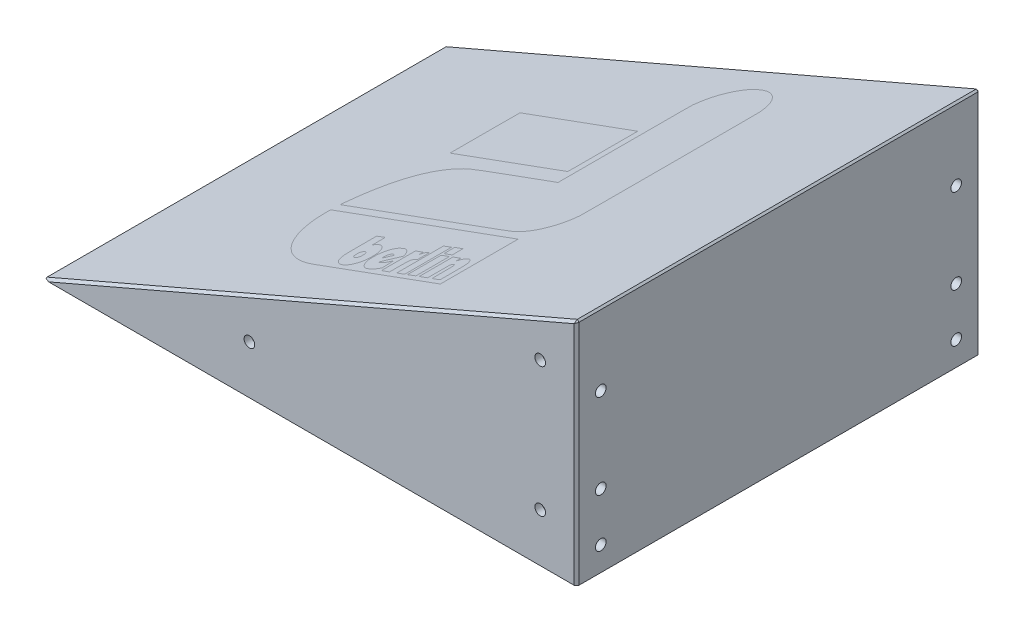
SolidWorks part; units mm, degrees
note: The reader was unsure of these and kept them because the rebuilt part matched: shared geometry of "Sketch16<3>".
ref_plane "Front Plane" through (0, 0, 0) normal (0, 0, 1) x (1, 0, 0)
ref_plane "Top Plane" through (0, 0, 0) normal (0, 1, 0) x (1, 0, 0)
ref_plane "Right Plane" through (0, 0, 0) normal (1, 0, 0) x (0, 0, -1)
sketch "Sketch1" plane through (0, 0, 0) normal (0, 0, 1) x (1, 0, 0)
  line L0 (0, 0) -> (-220.3974, 0)
  line L1 (-220.3974, 0) -> (0, 95)
  line L2 (0, 95) -> (0, 0)
  dimension "D1" = 240
extrude "Boss-Extrude1" add sketch "Sketch1" along normal blind 166.6667
ref_plane "Plane1" through (0, 0, 163.6667) normal (0, 0, 1) x (1, 0, 0)
sketch "Sketch2" plane through (0, 0, 163.6667) normal (0, 0, 1) x (1, 0, 0)
  line L0 (-5, 0) -> (-5, 87.4001)
  line L1 (-220.3974, 0) -> (0, 0) construction
  line L2 (-5, 87.4001) -> (-178.2213, 12.7348)
  line L3 (-178.2213, 12.7348) -> (-178.2213, 0)
  line L4 (-178.2213, 0) -> (-5, 0)
  line L5 (0, 95) -> (-220.3974, 0) construction
  line L6 (0, 0) -> (0, 95) construction
  dimension "D1" = 188.628
  dimension "D2" = 5
  dimension "D3" = 5
extrude "Cut-Extrude1" cut sketch "Sketch2" against normal offset from surface (160.6667 mm away) 3 up to face at (-73.4658, 31.6667, 0)
sketch "Sketch3" plane through (0, 0, 0) normal (1, 0, 0) x (0, 0, -1)
  line L0 (-156.6667, 0) -> (-156.6667, 95) construction
  line L1 (-166.6667, 0) -> (0, 0) construction
  line L2 (-166.6667, 95) -> (0, 95) construction
  line L3 (-166.6667, 0) -> (-166.6667, 95) construction
  line L4 (-83.3333, 95) -> (-83.3333, 0) construction
  line L5 (-10, 0) -> (-10, 95) construction
  circle A0 centre (-156.6667, 10) radius 2.2
  circle A1 centre (-156.6667, 65) radius 2.2
  circle A2 centre (-156.6667, 30) radius 2.2
  circle A3 centre (-10, 30) radius 2.2
  circle A4 centre (-10, 65) radius 2.2
  circle A5 centre (-10, 10) radius 2.2
  dimension "D2" = 4.4
  dimension "D3" = 10
  dimension "D4" = 20
  dimension "D5" = 30
  dimension "D1" = 10
extrude "Cut-Extrude2" cut sketch "Sketch3" against normal up to surface (5 mm away) up to face at (-5, 43.7, 83.3333)
sketch "Sketch4" plane through (0, 0, 0) normal (0, 0, -1) x (-1, 0, 0)
  line L0 (15, 0) -> (15, 88.5344) construction
  line L1 (220.3974, 0) -> (0, 0) construction
  line L2 (0, 95) -> (220.3974, 0) construction
  line L3 (0, 0) -> (0, 95) construction
  line L4 (15, 20) -> (135, 20) construction
  circle A0 centre (15, 73.5344) radius 2.2
  circle A1 centre (15, 20) radius 2.2
  circle A2 centre (135, 20) radius 2.2
  dimension "D1" = 4.4
  dimension "D2" = 20
  dimension "D3" = 15
  dimension "D4" = 15
  dimension "D5" = 120
extrude "Cut-Extrude3" cut sketch "Sketch4" against normal up to surface (163.6667 mm away)
ref_plane "Plane2" through (0, 0, 83.3333) normal (0, 0, -1) x (-1, 0, 0)
mirror "Mirror1" about plane through (0, 0, 83.3333) normal (0, 0, -1) of "Cut-Extrude3"
chamfer "Chamfer1" distance 1 angle 45 6 edges at (-220.3974, 0, 83.3333) (0, 95, 83.3333) (0, 47.5, 166.6667) (-110.1987, 47.5, 166.6667) (0, 47.5, 0) (-110.1987, 47.5, 0)
sketch "Sketch13" plane through (-166.8801, 23.068, 13.9635) normal (-0.3958, 0.9183, 0) x (0, 0, 1)
  line L0 (55.9477, 28.1093) -> (55.9477, 56.0832)
  line L1 (55.9477, 56.0832) -> (27.9739, 56.0832)
  line L2 (27.9739, 56.0832) -> (0, 56.0832)
  line L3 (0, 56.0832) -> (0, 96.1136)
  line L4 (0, 96.1136) -> (0, 136.144)
  line L5 (0, 136.144) -> (40.0304, 136.144)
  line L6 (40.0304, 136.144) -> (80.0608, 136.144)
  line L7 (80.0608, 136.144) -> (80.0608, 108.1701)
  line L8 (80.0608, 108.1701) -> (80.0608, 80.1962)
  line L9 (80.0608, 80.1962) -> (108.0347, 80.1962)
  line L10 (108.0347, 80.1962) -> (136.0085, 80.1962)
  line L11 (136.0085, 80.1962) -> (136.0085, 40.1658)
  line L12 (136.0085, 40.1658) -> (136.0085, 0.1354)
  line L13 (136.0085, 0.1354) -> (95.9781, 0.1354)
  line L14 (95.9781, 0.1354) -> (55.9477, 0.1354)
  line L15 (55.9477, 0.1354) -> (55.9477, 28.1093)
  line L16 (119.38, 5.285) -> (120.0235, 5.4406)
  line L17 (120.0235, 5.4406) -> (120.0235, 6.5278)
  line L18 (116.4971, 12.8693) -> (120.4299, 12.8693)
  line L19 (120.4299, 12.8693) -> (120.4288, 13.445)
  line L20 (119.3798, 5.285) -> (119.38, 5.285)
  line L21 (117.4134, 15.1659) -> (117.4853, 14.6304)
  line L22 (117.4853, 14.6304) -> (115.029, 14.6304)
  line L23 (130.3189, 17.2595) -> (130.3189, 18.5339)
  line L24 (130.3189, 18.5339) -> (129.0181, 18.7681)
  line L25 (84.9376, 11.9888) -> (84.9376, 18.6944)
  line L26 (84.9376, 18.6944) -> (83.3797, 18.6944)
  line L27 (83.3797, 18.6944) -> (81.8219, 18.6944)
  line L28 (81.8219, 18.6944) -> (81.8219, 11.9888)
  line L29 (81.8219, 11.9888) -> (81.8219, 5.2832)
  line L30 (81.8219, 5.2832) -> (83.3797, 5.2832)
  line L31 (83.3797, 5.2832) -> (84.9376, 5.2832)
  line L32 (84.9376, 5.2832) -> (84.9376, 11.9888)
  line L33 (95.7918, 15.6286) -> (96.1136, 15.2862)
  line L34 (96.1136, 15.2862) -> (96.1522, 10.2847)
  line L35 (96.1522, 10.2847) -> (96.1909, 5.2832)
  line L36 (96.1909, 5.2832) -> (97.744, 5.2832)
  line L37 (97.744, 5.2832) -> (99.2971, 5.2832)
  line L38 (99.2971, 5.2832) -> (99.2996, 8.5682)
  line L39 (103.4721, 10.1261) -> (103.5151, 5.2832)
  line L40 (103.5151, 5.2832) -> (105.0018, 5.2832)
  line L41 (105.0018, 5.2832) -> (106.4885, 5.2832)
  line L42 (106.4885, 5.2832) -> (106.4489, 10.7357)
  line L43 (99.574, 17.0612) -> (99.077, 16.2924)
  line L44 (99.077, 16.2924) -> (98.8423, 16.9531)
  line L45 (92.5097, 17.2277) -> (92.1175, 16.6093)
  line L46 (92.1175, 16.6093) -> (92.1175, 17.6519)
  line L47 (92.1175, 17.6519) -> (92.1175, 18.6944)
  line L48 (92.1175, 18.6944) -> (90.5597, 18.6944)
  line L49 (90.5597, 18.6944) -> (89.0018, 18.6944)
  line L50 (89.0018, 18.6944) -> (89.0018, 11.9888)
  line L51 (89.0018, 11.9888) -> (89.0018, 5.2832)
  line L52 (89.0018, 5.2832) -> (90.5503, 5.2832)
  line L53 (90.5503, 5.2832) -> (92.0987, 5.2832)
  line L54 (92.0987, 5.2832) -> (92.1453, 9.1101)
  line L55 (84.9376, 23.1648) -> (84.9376, 24.6549)
  line L56 (84.9376, 24.6549) -> (83.3797, 24.6549)
  line L57 (83.3797, 24.6549) -> (81.8219, 24.6549)
  line L58 (81.8219, 24.6549) -> (81.8219, 23.1648)
  line L59 (81.8219, 23.1648) -> (81.8219, 21.6746)
  line L60 (81.8219, 21.6746) -> (83.3797, 21.6746)
  line L61 (83.3797, 21.6746) -> (84.9376, 21.6746)
  line L62 (84.9376, 21.6746) -> (84.9376, 23.1648)
  line L63 (80.0277, 68.1058) -> (80.0623, 80.0608)
  line L64 (80.0623, 80.0608) -> (68.0727, 80.0608)
  line L65 (68.0727, 80.0608) -> (56.0832, 80.0608)
  line L66 (56.0832, 80.0608) -> (56.0832, 68.0712)
  line L67 (56.0832, 68.0712) -> (56.0832, 56.0817)
  line L68 (56.0832, 56.0817) -> (68.0381, 56.1163)
  line L69 (68.0381, 56.1163) -> (79.9931, 56.1509)
  line L70 (79.9931, 56.1509) -> (80.0277, 68.1058)
  line L71 (56.0832, 56.0817) -> (55.9477, 56.0832)
  line L72 (80.0623, 80.0608) -> (80.0608, 80.2508)
  spline S0 degree 3 poles (120.0235, 6.5278) (120.0235, 7.4768) (119.9954, 7.6043) (119.8028, 7.5304) knots 0 0 0 0 1 1 1 1
  spline S1 degree 3 poles (119.8028, 7.5304) (119.096, 7.2592) (118.2565, 7.1534) (117.2109, 7.2036) knots 0 0 0 0 1 1 1 1
  spline S2 degree 3 poles (117.2109, 7.2036) (116.2244, 7.2511) (115.9063, 7.3264) (115.3017, 7.6558) knots 0 0 0 0 1 1 1 1
  spline S3 degree 3 poles (115.3017, 7.6558) (113.9807, 8.3756) (112.9036, 9.9548) (112.5572, 11.6798) knots 0 0 0 0 1 1 1 1
  spline S4 degree 3 poles (112.5572, 11.6798) (112.3015, 12.9531) (112.024, 12.8693) (116.4971, 12.8693) knots 0 0 0 0 1 1 1 1
  spline S5 degree 3 poles (120.4288, 13.445) (120.4268, 15.0769) (119.8192, 16.8204) (118.9624, 17.6545) knots 0 0 0 0 1 1 1 1
  spline S6 degree 3 poles (118.9624, 17.6545) (118.689, 17.9206) (118.0996, 18.3072) (117.6526, 18.5136) knots 0 0 0 0 1 1 1 1
  spline S7 degree 3 poles (117.6526, 18.5136) (116.9232, 18.8503) (116.6868, 18.8893) (115.3496, 18.8932) knots 0 0 0 0 1 1 1 1
  spline S8 degree 3 poles (115.3496, 18.8932) (113.601, 18.8983) (112.619, 18.6494) (111.7388, 17.9781) knots 0 0 0 0 1 1 1 1
  spline S9 degree 3 poles (111.7388, 17.9781) (110.8801, 17.3232) (110.3098, 16.4939) (109.966, 15.4003) knots 0 0 0 0 1 1 1 1
  spline S10 degree 3 poles (109.966, 15.4003) (109.5683, 14.1354) (109.537, 11.2699) (109.9059, 9.889) knots 0 0 0 0 1 1 1 1
  spline S11 degree 3 poles (109.9059, 9.889) (110.5643, 7.4241) (112.0357, 5.8283) (114.2123, 5.2184) knots 0 0 0 0 1 1 1 1
  spline S12 degree 3 poles (114.2123, 5.2184) (115.0598, 4.9809) (118.2945, 5.0226) (119.3798, 5.285) knots 0 0 0 0 1 1 1 1
  spline S13 degree 3 poles (112.5728, 14.8379) (112.5728, 15.2621) (112.9536, 15.9345) (113.4314, 16.354) knots 0 0 0 0 1 1 1 1
  spline S14 degree 3 poles (113.4314, 16.354) (114.8968, 17.6406) (117.1726, 16.9616) (117.4134, 15.1659) knots 0 0 0 0 1 1 1 1
  spline S15 degree 3 poles (115.029, 14.6304) (112.9131, 14.6304) (112.5728, 14.6591) (112.5728, 14.8379) knots 0 0 0 0 1 1 1 1
  spline S16 degree 3 poles (128.0837, 5.1959) (130.1184, 5.7381) (131.1308, 6.9611) (131.1274, 8.873) knots 0 0 0 0 1 1 1 1
  spline S17 degree 3 poles (131.1274, 8.873) (131.1244, 10.659) (130.5305, 11.4345) (127.802, 13.2159) knots 0 0 0 0 1 1 1 1
  spline S18 degree 3 poles (127.802, 13.2159) (125.8156, 14.5128) (125.3067, 14.9859) (125.3067, 15.5356) knots 0 0 0 0 1 1 1 1
  spline S19 degree 3 poles (125.3067, 15.5356) (125.3067, 16.2783) (126.7192, 16.9245) (127.9105, 16.7268) knots 0 0 0 0 1 1 1 1
  spline S20 degree 3 poles (127.9105, 16.7268) (128.2293, 16.6739) (128.8784, 16.4854) (129.3529, 16.3078) knots 0 0 0 0 1 1 1 1
  spline S21 degree 3 poles (129.3529, 16.3078) (129.8275, 16.1303) (130.2389, 15.985) (130.2673, 15.985) knots 0 0 0 0 1 1 1 1
  spline S22 degree 3 poles (130.2673, 15.985) (130.2957, 15.985) (130.3189, 16.5585) (130.3189, 17.2595) knots 0 0 0 0 1 1 1 1
  spline S23 degree 3 poles (129.0181, 18.7681) (125.2165, 19.4526) (122.5963, 17.9842) (122.6016, 15.1722) knots 0 0 0 0 1 1 1 1
  spline S24 degree 3 poles (122.6016, 15.1722) (122.6047, 13.5145) (123.3273, 12.5517) (125.8526, 10.8401) knots 0 0 0 0 1 1 1 1
  spline S25 degree 3 poles (125.8526, 10.8401) (127.7723, 9.539) (128.2869, 9.0543) (128.2869, 8.5476) knots 0 0 0 0 1 1 1 1
  spline S26 degree 3 poles (128.2869, 8.5476) (128.2869, 7.2086) (125.4698, 6.9556) (122.8344, 8.0578) knots 0 0 0 0 1 1 1 1
  spline S27 degree 3 poles (122.8344, 8.0578) (122.6177, 8.1484) (122.5973, 8.0392) (122.5973, 6.7878) knots 0 0 0 0 1 1 1 1
  spline S28 degree 3 poles (122.5973, 6.7878) (122.5973, 5.7874) (122.6429, 5.4163) (122.7667, 5.4099) knots 0 0 0 0 1 1 1 1
  spline S29 degree 3 poles (122.7667, 5.4099) (122.8598, 5.4053) (123.3017, 5.3188) (123.7488, 5.2181) knots 0 0 0 0 1 1 1 1
  spline S30 degree 3 poles (123.7488, 5.2181) (124.8105, 4.9789) (127.2228, 4.9665) (128.0837, 5.1959) knots 0 0 0 0 1 1 1 1
  spline S31 degree 3 poles (92.1453, 9.1101) (92.1899, 12.7599) (92.207, 12.9747) (92.5133, 13.7498) knots 0 0 0 0 1 1 1 1
  spline S32 degree 3 poles (92.5133, 13.7498) (92.999, 14.9787) (93.5089, 15.6452) (94.1635, 15.9072) knots 0 0 0 0 1 1 1 1
  spline S33 degree 3 poles (94.1635, 15.9072) (94.8473, 16.1808) (95.3543, 16.0941) (95.7918, 15.6286) knots 0 0 0 0 1 1 1 1
  spline S34 degree 3 poles (99.2996, 8.5682) (99.3022, 12.0563) (99.4174, 13.0342) (99.9806, 14.3433) knots 0 0 0 0 1 1 1 1
  spline S35 degree 3 poles (99.9806, 14.3433) (100.5254, 15.6097) (101.6839, 16.3432) (102.5638, 15.9787) knots 0 0 0 0 1 1 1 1
  spline S36 degree 3 poles (102.5638, 15.9787) (103.3998, 15.6324) (103.4245, 15.4734) (103.4721, 10.1261) knots 0 0 0 0 1 1 1 1
  spline S37 degree 3 poles (106.4489, 10.7357) (106.4099, 16.0999) (106.4042, 16.1992) (106.0972, 16.8656) knots 0 0 0 0 1 1 1 1
  spline S38 degree 3 poles (106.0972, 16.8656) (105.5361, 18.0835) (104.6197, 18.7738) (103.367, 18.9222) knots 0 0 0 0 1 1 1 1
  spline S39 degree 3 poles (103.367, 18.9222) (101.906, 19.0952) (100.4161, 18.3642) (99.574, 17.0612) knots 0 0 0 0 1 1 1 1
  spline S40 degree 3 poles (98.8423, 16.9531) (98.5273, 17.84) (97.8459, 18.4967) (96.9708, 18.7566) knots 0 0 0 0 1 1 1 1
  spline S41 degree 3 poles (96.9708, 18.7566) (95.1569, 19.2952) (93.4499, 18.7102) (92.5097, 17.2277) knots 0 0 0 0 1 1 1 1
sketch "Sketch14" plane through (0, 0, 166.6667) normal (0, 0, 1) x (1, 0, 0)
  circle A0 centre (-135, 20) radius 2.85
  circle A1 centre (-15, 20) radius 2.85
  circle A2 centre (-15, 73.5344) radius 2.85
  dimension "D1" = 5.7
extrude "Einschmelzgewinde" [suppressed] cut sketch "Sketch14" against normal through all
chamfer "Chamfer2" [suppressed] distance 0.6 angle 45
sketch "Sketch16" plane through (-159.9623, 26.0499, 9.8989) normal (-0.3958, 0.9183, 0) x (0, 0, 1)
  line L0 (108.335, 94.9617) -> (108.3883, 95.2128)
  line L1 (108.3883, 95.2128) -> (124.4039, 95.2128)
  line L2 (124.4039, 95.2128) -> (140.4193, 95.2128)
  line L3 (140.4193, 95.2128) -> (140.4193, 94.9494)
  line L4 (119.0172, 42.3273) -> (119.2954, 41.6386)
  line L5 (119.2954, 41.6386) -> (116.6024, 41.6087)
  line L6 (116.6024, 41.6087) -> (113.9093, 41.5788)
  line L7 (113.9093, 41.5788) -> (113.7809, 40.1278)
  line L8 (113.5898, 37.9791) -> (113.5271, 37.2814)
  line L9 (113.5271, 37.2814) -> (119.8706, 37.2814)
  line L10 (128.4948, 60.8777) -> (128.1231, 60.82)
  line L11 (128.1231, 60.82) -> (128.6416, 60.2657)
  line L12 (135.3473, 66.6099) -> (135.4007, 66.861)
  line L13 (135.4007, 66.861) -> (131.7353, 66.861)
  line L14 (126.2622, 68.6507) -> (126.2183, 69.4283)
  line L15 (126.2183, 69.4283) -> (123.6492, 69.4283)
  line L16 (123.6492, 69.4283) -> (121.0801, 69.4283)
  line L17 (121.0801, 69.4283) -> (121.1565, 68.8528)
  line L18 (122.6716, 66.8701) -> (123.1739, 66.6427)
  line L19 (123.1739, 66.6427) -> (122.2495, 66.6402)
  line L20 (121.0826, 64.5448) -> (120.9319, 62.731)
  line L21 (120.9319, 62.731) -> (127.9311, 62.731)
  line L22 (127.9311, 62.731) -> (134.9303, 62.731)
  line L23 (134.9303, 62.731) -> (134.9938, 63.1496)
  line L24 (136.0281, 73.7537) -> (136.097, 74.4513)
  line L25 (136.097, 74.4513) -> (126.4447, 74.4513)
  line L26 (126.4447, 74.4513) -> (116.7925, 74.4513)
  line L27 (116.7925, 74.4513) -> (116.6573, 73.0281)
  line L28 (116.4561, 71.0189) -> (116.3901, 70.4329)
  line L29 (116.3901, 70.4329) -> (126.0443, 70.4329)
  line L30 (126.0443, 70.4329) -> (135.6986, 70.4329)
  line L31 (135.6986, 70.4329) -> (135.8289, 71.7445)
  line L32 (121.5481, 79.7835) -> (121.5554, 80.0371)
  line L33 (121.5554, 80.0371) -> (119.3509, 80.0068)
  line L34 (119.3509, 80.0068) -> (117.1463, 79.9766)
  line L35 (117.1463, 79.9766) -> (116.9582, 78.2464)
  line L36 (116.7628, 76.1512) -> (116.7557, 75.7861)
  line L37 (116.7557, 75.7861) -> (118.9602, 75.8163)
  line L38 (118.9602, 75.8163) -> (121.1647, 75.8465)
  line L39 (121.1647, 75.8465) -> (121.3527, 77.6883)
  line L40 (129.5857, 80.0053) -> (122.7274, 79.9765)
  line L41 (122.7274, 79.9765) -> (122.5423, 78.2464)
  line L42 (122.347, 76.1535) -> (122.3367, 75.7907)
  line L43 (122.3367, 75.7907) -> (129.2522, 75.7907)
  line L44 (129.2522, 75.7907) -> (136.1676, 75.7907)
  line L45 (136.1676, 75.7907) -> (136.2258, 76.1535)
  line L46 (137.7371, 91.7805) -> (137.7405, 92.199)
  line L47 (137.7405, 92.199) -> (132.7274, 92.199)
  line L48 (124.5456, 86.2731) -> (125.1453, 85.725)
  line L49 (125.1453, 85.725) -> (124.1875, 85.725)
  line L50 (122.8971, 82.0136) -> (122.895, 81.7067)
  line L51 (122.895, 81.7067) -> (129.8134, 81.7067)
  line L52 (129.8134, 81.7067) -> (136.7318, 81.7067)
  line L53 (136.7318, 81.7067) -> (136.7861, 81.9578)
  line L54 (70.7202, 71.6869) -> (70.7883, 72.2154)
  line L55 (70.7883, 72.2154) -> (43.3471, 72.2485)
  line L56 (99.7225, 44.2299) -> (95.6092, 1.4511)
  line L57 (95.6092, 1.4511) -> (95.3273, 1.4581)
  line L58 (34.5525, 68.1726) -> (34.6162, 68.647)
  line L59 (34.6162, 68.647) -> (49.0085, 68.647)
  line L60 (57.7572, 9.739) -> (57.7039, 9.4878)
  line L61 (57.7039, 9.4878) -> (43.3069, 9.4878)
  spline S0 degree 3 poles (99.9288, 1.0941) (99.3751, 1.126) (99.3428, 1.1445) (99.3424, 1.429) knots 0 0 0 0 1 1 1 1
  spline S1 degree 3 poles (99.3424, 1.429) (99.342, 1.8216) (108.2652, 94.6324) (108.335, 94.9617) knots 0 0 0 0 1 1 1 1
  spline S2 degree 3 poles (140.4193, 94.9494) (140.4193, 94.8046) (139.093, 80.8784) (137.4719, 64.0025) knots 0 0 0 0 1 1 1 1
  spline S3 degree 3 poles (137.4719, 64.0025) (135.8509, 47.1265) (134.4666, 32.6408) (134.3957, 31.812) knots 0 0 0 0 1 1 1 1
  spline S4 degree 3 poles (134.3957, 31.812) (133.88, 25.7773) (131.6141, 19.7739) (127.9922, 14.8456) knots 0 0 0 0 1 1 1 1
  spline S5 degree 3 poles (127.9922, 14.8456) (122.843, 7.8393) (115.2416, 3.113) (106.654, 1.5783) knots 0 0 0 0 1 1 1 1
  spline S6 degree 3 poles (106.654, 1.5783) (104.6505, 1.2203) (101.5789, 0.9991) (99.9288, 1.0941) knots 0 0 0 0 1 1 1 1
  spline S7 degree 3 poles (127.1959, 37.4526) (129.6932, 37.8881) (131.5617, 39.1703) (132.5472, 41.1247) knots 0 0 0 0 1 1 1 1
  spline S8 degree 3 poles (132.5472, 41.1247) (133.7329, 43.4761) (133.4378, 45.9391) (131.7703, 47.6089) knots 0 0 0 0 1 1 1 1
  spline S9 degree 3 poles (131.7703, 47.6089) (130.9869, 48.3934) (130.1037, 48.8893) (128.8626, 49.2415) knots 0 0 0 0 1 1 1 1
  spline S10 degree 3 poles (128.8626, 49.2415) (127.6313, 49.5909) (125.3664, 49.593) (124.0921, 49.2458) knots 0 0 0 0 1 1 1 1
  spline S11 degree 3 poles (124.0921, 49.2458) (121.9286, 48.6564) (119.9287, 47.1652) (119.1929, 45.5927) knots 0 0 0 0 1 1 1 1
  spline S12 degree 3 poles (119.1929, 45.5927) (118.6846, 44.5065) (118.6202, 43.3102) (119.0172, 42.3273) knots 0 0 0 0 1 1 1 1
  spline S13 degree 3 poles (113.7809, 40.1278) (113.7103, 39.3297) (113.6243, 38.3628) (113.5898, 37.9791) knots 0 0 0 0 1 1 1 1
  spline S14 degree 3 poles (119.8706, 37.2814) (125.0701, 37.2814) (126.3913, 37.3123) (127.1959, 37.4526) knots 0 0 0 0 1 1 1 1
  spline S15 degree 3 poles (124.683, 41.8302) (124.2066, 42.0695) (123.7878, 42.6706) (123.7878, 43.115) knots 0 0 0 0 1 1 1 1
  spline S16 degree 3 poles (123.7878, 43.115) (123.7878, 44.0733) (124.8448, 44.9018) (126.061, 44.8967) knots 0 0 0 0 1 1 1 1
  spline S17 degree 3 poles (126.061, 44.8967) (126.4376, 44.8951) (126.8965, 44.8353) (127.0806, 44.7637) knots 0 0 0 0 1 1 1 1
  spline S18 degree 3 poles (127.0806, 44.7637) (128.5131, 44.2069) (128.3984, 42.4386) (126.8889, 41.808) knots 0 0 0 0 1 1 1 1
  spline S19 degree 3 poles (126.8889, 41.808) (126.3234, 41.5718) (125.1742, 41.5834) (124.683, 41.8302) knots 0 0 0 0 1 1 1 1
  spline S20 degree 3 poles (129.0898, 50.3881) (130.4091, 50.7397) (131.5756, 51.4157) (132.5562, 52.3968) knots 0 0 0 0 1 1 1 1
  spline S21 degree 3 poles (132.5562, 52.3968) (133.5933, 53.4344) (134.0718, 54.2866) (134.3479, 55.5873) knots 0 0 0 0 1 1 1 1
  spline S22 degree 3 poles (134.3479, 55.5873) (134.5774, 56.6687) (134.5006, 58.2812) (134.1754, 59.2082) knots 0 0 0 0 1 1 1 1
  spline S23 degree 3 poles (134.1754, 59.2082) (133.991, 59.7338) (133.3874, 60.9544) (133.2151, 61.15) knots 0 0 0 0 1 1 1 1
  spline S24 degree 3 poles (133.2151, 61.15) (133.1738, 61.1968) (128.9995, 60.9561) (128.4948, 60.8777) knots 0 0 0 0 1 1 1 1
  spline S25 degree 3 poles (128.6416, 60.2657) (129.2264, 59.6405) (129.7617, 58.5889) (129.9165, 57.7615) knots 0 0 0 0 1 1 1 1
  spline S26 degree 3 poles (129.9165, 57.7615) (130.0205, 57.2053) (129.8952, 56.0797) (129.7076, 55.8848) knots 0 0 0 0 1 1 1 1
  spline S27 degree 3 poles (129.7076, 55.8848) (129.6582, 55.8336) (128.5998, 57.0391) (127.3555, 58.5637) knots 0 0 0 0 1 1 1 1
  spline S28 degree 3 poles (127.3555, 58.5637) (126.1112, 60.0884) (125.0269, 61.408) (124.9459, 61.4961) knots 0 0 0 0 1 1 1 1
  spline S29 degree 3 poles (124.9459, 61.4961) (124.8192, 61.6341) (124.6539, 61.5841) (123.763, 61.1388) knots 0 0 0 0 1 1 1 1
  spline S30 degree 3 poles (123.763, 61.1388) (122.0214, 60.2682) (120.894, 59.1315) (120.2496, 57.5965) knots 0 0 0 0 1 1 1 1
  spline S31 degree 3 poles (120.2496, 57.5965) (119.9789, 56.9516) (119.9446, 56.7282) (119.941, 55.5873) knots 0 0 0 0 1 1 1 1
  spline S32 degree 3 poles (119.941, 55.5873) (119.9372, 54.3693) (119.9552, 54.2649) (120.2957, 53.546) knots 0 0 0 0 1 1 1 1
  spline S33 degree 3 poles (120.2957, 53.546) (121.0988, 51.8507) (122.7102, 50.7216) (124.9598, 50.278) knots 0 0 0 0 1 1 1 1
  spline S34 degree 3 poles (124.9598, 50.278) (125.9457, 50.0835) (128.1696, 50.1428) (129.0898, 50.3881) knots 0 0 0 0 1 1 1 1
  spline S35 degree 3 poles (125.3236, 54.4067) (124.3448, 54.756) (123.9481, 55.2867) (124.0422, 56.1209) knots 0 0 0 0 1 1 1 1
  spline S36 degree 3 poles (124.0422, 56.1209) (124.104, 56.6693) (124.4381, 57.2058) (124.7178, 57.2058) knots 0 0 0 0 1 1 1 1
  spline S37 degree 3 poles (124.7178, 57.2058) (124.8169, 57.2058) (125.4055, 56.5799) (126.0256, 55.815) knots 0 0 0 0 1 1 1 1
  spline S38 degree 3 poles (126.0256, 55.815) (126.9915, 54.6235) (127.124, 54.4126) (126.9495, 54.3438) knots 0 0 0 0 1 1 1 1
  spline S39 degree 3 poles (126.9495, 54.3438) (126.6189, 54.2136) (125.7731, 54.2463) (125.3236, 54.4067) knots 0 0 0 0 1 1 1 1
  spline S40 degree 3 poles (134.9938, 63.1496) (135.0287, 63.3799) (135.1105, 64.1961) (135.1756, 64.9635) knots 0 0 0 0 1 1 1 1
  spline S41 degree 3 poles (135.1756, 64.9635) (135.2407, 65.7309) (135.3179, 66.4718) (135.3473, 66.6099) knots 0 0 0 0 1 1 1 1
  spline S42 degree 3 poles (131.7353, 66.861) (127.6607, 66.861) (127.2203, 66.919) (126.6331, 67.5319) knots 0 0 0 0 1 1 1 1
  spline S43 degree 3 poles (126.6331, 67.5319) (126.3487, 67.8287) (126.3004, 67.9743) (126.2622, 68.6507) knots 0 0 0 0 1 1 1 1
  spline S44 degree 3 poles (121.1565, 68.8528) (121.2855, 67.8803) (121.7327, 67.2951) (122.6716, 66.8701) knots 0 0 0 0 1 1 1 1
  spline S45 degree 3 poles (122.2495, 66.6402) (121.6108, 66.6385) (121.3109, 66.5946) (121.2792, 66.4982) knots 0 0 0 0 1 1 1 1
  spline S46 degree 3 poles (121.2792, 66.4982) (121.2539, 66.4215) (121.1654, 65.5424) (121.0826, 64.5448) knots 0 0 0 0 1 1 1 1
  spline S47 degree 3 poles (135.8289, 71.7445) (135.9006, 72.4658) (135.9902, 73.37) (136.0281, 73.7537) knots 0 0 0 0 1 1 1 1
  spline S48 degree 3 poles (116.6573, 73.0281) (116.583, 72.2454) (116.4924, 71.3412) (116.4561, 71.0189) knots 0 0 0 0 1 1 1 1
  spline S49 degree 3 poles (121.3527, 77.6883) (121.4562, 78.7013) (121.5441, 79.6441) (121.5481, 79.7835) knots 0 0 0 0 1 1 1 1
  spline S50 degree 3 poles (116.9582, 78.2464) (116.8547, 77.2949) (116.7668, 76.352) (116.7628, 76.1512) knots 0 0 0 0 1 1 1 1
  spline S51 degree 3 poles (136.2258, 76.1535) (136.401, 77.2459) (136.6154, 79.8626) (136.5362, 79.9418) knots 0 0 0 0 1 1 1 1
  spline S52 degree 3 poles (136.5362, 79.9418) (136.4854, 79.9925) (133.3577, 80.0211) (129.5857, 80.0053) knots 0 0 0 0 1 1 1 1
  spline S53 degree 3 poles (122.5423, 78.2464) (122.4405, 77.2948) (122.3526, 76.353) (122.347, 76.1535) knots 0 0 0 0 1 1 1 1
  spline S54 degree 3 poles (136.7861, 81.9578) (136.8399, 82.2056) (137.183, 85.5381) (137.1826, 85.8087) knots 0 0 0 0 1 1 1 1
  spline S55 degree 3 poles (137.1826, 85.8087) (137.1824, 85.9179) (136.2511, 85.9483) (132.8989, 85.9483) knots 0 0 0 0 1 1 1 1
  spline S56 degree 3 poles (132.8989, 85.9483) (130.543, 85.9483) (128.4592, 85.9795) (128.2682, 86.0177) knots 0 0 0 0 1 1 1 1
  spline S57 degree 3 poles (128.2682, 86.0177) (127.0674, 86.2579) (127.063, 87.6163) (128.2619, 87.9601) knots 0 0 0 0 1 1 1 1
  spline S58 degree 3 poles (128.2619, 87.9601) (128.4801, 88.0227) (130.5078, 88.0691) (133.0237, 88.0691) knots 0 0 0 0 1 1 1 1
  spline S59 degree 3 poles (133.0237, 88.0691) (135.4337, 88.0691) (137.4066, 88.1067) (137.4079, 88.1528) knots 0 0 0 0 1 1 1 1
  spline S60 degree 3 poles (137.4079, 88.1528) (137.4092, 88.1988) (137.483, 88.9397) (137.572, 89.7992) knots 0 0 0 0 1 1 1 1
  spline S61 degree 3 poles (137.572, 89.7992) (137.661, 90.6587) (137.7353, 91.5502) (137.7371, 91.7805) knots 0 0 0 0 1 1 1 1
  spline S62 degree 3 poles (132.7274, 92.199) (127.089, 92.199) (126.5298, 92.1453) (125.1613, 91.4718) knots 0 0 0 0 1 1 1 1
  spline S63 degree 3 poles (125.1613, 91.4718) (122.8791, 90.3488) (122.6063, 88.0455) (124.5456, 86.2731) knots 0 0 0 0 1 1 1 1
  spline S64 degree 3 poles (124.1875, 85.725) (123.3506, 85.725) (123.2295, 85.7004) (123.2276, 85.5297) knots 0 0 0 0 1 1 1 1
  spline S65 degree 3 poles (123.2276, 85.5297) (123.2263, 85.4222) (123.152, 84.6562) (123.0623, 83.8275) knots 0 0 0 0 1 1 1 1
  spline S66 degree 3 poles (123.0623, 83.8275) (122.9727, 82.9987) (122.8983, 82.1824) (122.8971, 82.0136) knots 0 0 0 0 1 1 1 1
  spline S67 degree 3 poles (93.4827, 1.7944) (86.4283, 3.2812) (80.6671, 5.6886) (76.3031, 8.9734) knots 0 0 0 0 1 1 1 1
  spline S68 degree 3 poles (76.3031, 8.9734) (70.7052, 13.1868) (67.548, 18.7815) (66.8534, 25.7183) knots 0 0 0 0 1 1 1 1
  spline S69 degree 3 poles (66.8534, 25.7183) (66.5763, 28.4865) (66.7076, 30.2692) (68.7462, 51.4015) knots 0 0 0 0 1 1 1 1
  spline S70 degree 3 poles (68.7462, 51.4015) (69.7944, 62.2678) (70.6827, 71.3963) (70.7202, 71.6869) knots 0 0 0 0 1 1 1 1
  spline S71 degree 3 poles (43.3471, 72.2485) (17.4254, 72.2797) (15.8597, 72.2927) (15.0689, 72.4815) knots 0 0 0 0 1 1 1 1
  spline S72 degree 3 poles (15.0689, 72.4815) (11.9447, 73.2276) (9.4071, 74.5667) (7.3245, 76.5682) knots 0 0 0 0 1 1 1 1
  spline S73 degree 3 poles (7.3245, 76.5682) (4.9723, 78.8288) (3.4319, 81.5645) (2.7342, 84.7204) knots 0 0 0 0 1 1 1 1
  spline S74 degree 3 poles (2.7342, 84.7204) (2.4434, 86.0356) (2.3829, 89.1189) (2.6198, 90.5436) knots 0 0 0 0 1 1 1 1
  spline S75 degree 3 poles (2.6198, 90.5436) (3.7932, 97.5996) (9.4174, 102.8991) (16.5757, 103.6937) knots 0 0 0 0 1 1 1 1
  spline S76 degree 3 poles (16.5757, 103.6937) (17.3779, 103.7828) (27.8674, 103.807) (53.8572, 103.7797) knots 0 0 0 0 1 1 1 1
  spline S77 degree 3 poles (53.8572, 103.7797) (87.7707, 103.7441) (90.0815, 103.7296) (90.9712, 103.5465) knots 0 0 0 0 1 1 1 1
  spline S78 degree 3 poles (90.9712, 103.5465) (97.1672, 102.2714) (101.8162, 97.8564) (103.3845, 91.7579) knots 0 0 0 0 1 1 1 1
  spline S79 degree 3 poles (103.3845, 91.7579) (103.6569, 90.6984) (103.7266, 90.1608) (103.7759, 88.7388) knots 0 0 0 0 1 1 1 1
  spline S80 degree 3 poles (103.7759, 88.7388) (103.8334, 87.0779) (103.6712, 85.2972) (99.7225, 44.2299) knots 0 0 0 0 1 1 1 1
  spline S81 degree 3 poles (95.3273, 1.4581) (95.1722, 1.4619) (94.3422, 1.6133) (93.4827, 1.7944) knots 0 0 0 0 1 1 1 1
  spline S82 degree 3 poles (28.9099, 9.5662) (28.9099, 9.7404) (34.4934, 67.7329) (34.5525, 68.1726) knots 0 0 0 0 1 1 1 1
  spline S83 degree 3 poles (49.0085, 68.647) (62.6406, 68.647) (63.4009, 68.6366) (63.4019, 68.4516) knots 0 0 0 0 1 1 1 1
  spline S84 degree 3 poles (63.4019, 68.4516) (63.4037, 68.1366) (57.8158, 10.015) (57.7572, 9.739) knots 0 0 0 0 1 1 1 1
  spline S85 degree 3 poles (43.3069, 9.4878) (35.3885, 9.4878) (28.9099, 9.5231) (28.9099, 9.5662) knots 0 0 0 0 1 1 1 1
extrude "Cut-Extrude4" cut sketch "Sketch16" against normal blind 1 contours S81 L57 L56 S80 S79 S78 S77 S76 S75 S74 S73 S72 S71 L55 L54 S70 S69 S68 S67 | S6 S5 S4 S3 S2 L3 L2 L1 L0 S1 S0 S66 S65 S64 L49 L48 S63 S62 L47 L46 S61 S60 S59 S58 S57 S56 S55 S54 L53 L52 L51 L50 S53 L41 L40 S52 S51 L45 L44 L43 L42 S50 L35 L34 L33 L32 S49 L39 | S85 L61 L60 S84 S83 L59 L58 S82 | S19 S18 S17 S16 S15 | S39 S38 S37 S36 S35
extrude "Boss-Extrude2" add sketch "Sketch16<3>" against normal up to surface (1 mm away) separate body contours S81 L57 L56 S80 S79 S78 S77 S76 S75 S74 S73 S72 S71 L55 L54 S70 S69 S68 S67 | S85 L61 L60 S84 S83 L59 L58 S82 | S6 S5 S4 S3 S2 L3 L2 L1 L0 S1 S0 S66 S65 S64 L49 L48 S63 S62 L47 L46 S61 S60 S59 S58 S57 S56 S55 S54 L53 L52 L51 L50 S53 L41 L40 S52 S51 L45 L44 L43 L42 S50 L35 L34 L33 L32 S49 L39 | S39 S38 S37 S36 S35 | S19 S18 S17 S16 S15
sketch "Sketch16<3>" plane through (-159.9623, 26.0499, 9.8989) normal (-0.3958, 0.9183, 0) x (0, 0, 1) same geometry as "Sketch16"
